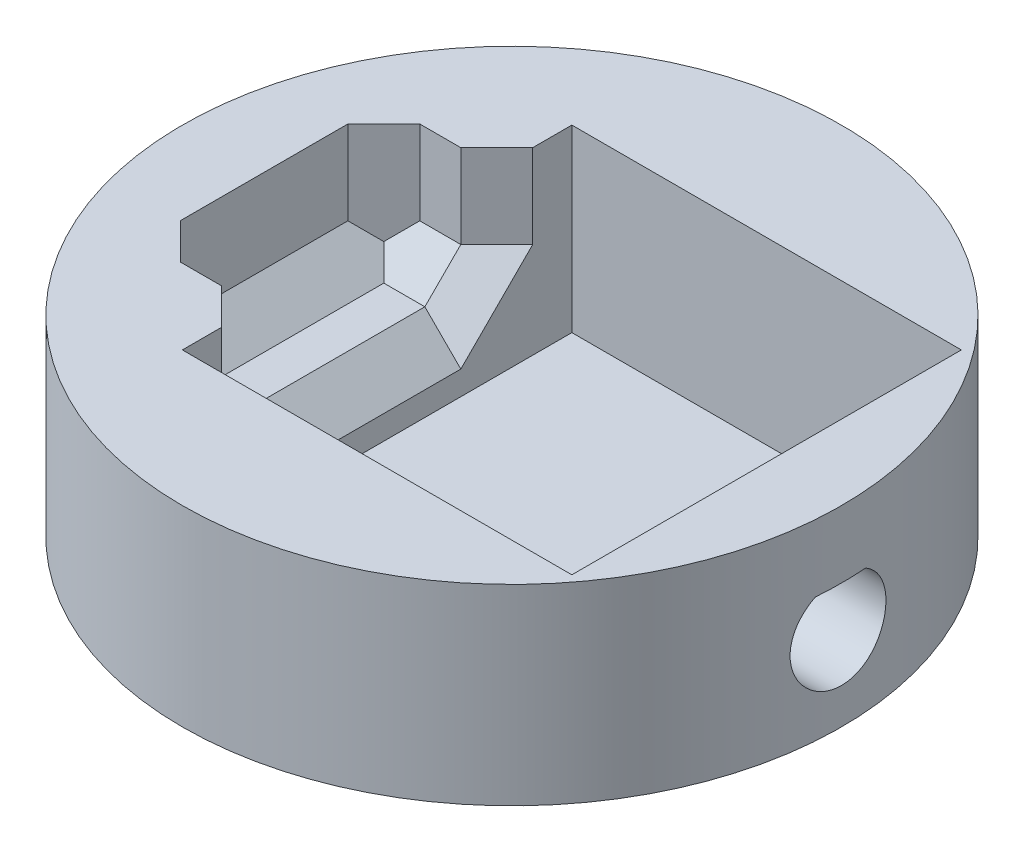
SolidWorks part; units mm, degrees
ref_plane "Front Plane" through (0, 0, 0) normal (0, 0, 1) x (1, 0, 0)
ref_plane "Top Plane" through (0, 0, 0) normal (0, 1, 0) x (1, 0, 0)
ref_plane "Right Plane" through (0, 0, 0) normal (1, 0, 0) x (0, 0, -1)
sketch "Sketch1" plane through (0, 0, 0) normal (0, 1, 0) x (1, 0, 0)
  circle A0 centre (0, 0) radius 27.5
  dimension "D1" = 55
extrude "Boss-Extrude1" add sketch "Sketch1" along normal blind 16
sketch "Sketch3" plane through (0, 16, 0) normal (0, 1, 0) x (1, 0, 0)
  line L0 (21.25, 0) -> (27.5, 0) construction
  line L1 (-11.25, -16.25) -> (16.25, -16.25)
  line L2 (-16.25, -16.25) -> (-16.25, 16.25) construction
  line L3 (-11.25, 16.25) -> (16.25, 16.25) construction
  line L4 (16.25, -16.25) -> (16.25, -1.9281) construction
  line L5 (-11.25, -11.25) -> (0, 0) construction
  line L6 (-11.25, 11.25) -> (0, 0) construction
  line L7 (0, 0) -> (16.25, 0) construction
  line L8 (21.25, 0) -> (27.5, 0) construction
  line L9 (-16.25, 16.25) -> (-11.25, 16.25) construction
  line L10 (16.25, 16.25) -> (21.25, 16.25)
  line L11 (16.25, 0) -> (16.25, -16.25) construction
  line L12 (16.25, -16.25) -> (21.25, -16.25)
  line L13 (21.25, 16.25) -> (21.25, -16.25)
  line L14 (-16.25, 16.25) -> (-11.25, 16.25) construction
  line L15 (-16.25, 16.25) -> (-16.25, -16.25) construction
  line L16 (-16.25, -16.25) -> (-11.25, -16.25) construction
  line L17 (-11.25, 16.25) -> (-11.25, -16.25)
  line L18 (-16.25, 16.25) -> (-11.25, 16.25) construction
  line L19 (-16.25, 16.25) -> (-11.25, 11.25) construction
  line L20 (-16.25, -16.25) -> (-11.25, -11.25) construction
  line L21 (-16.25, -16.25) -> (-11.25, -16.25) construction
  line L22 (0, 0) -> (16.25, 0) construction
  line L23 (16.25, 6.8206) -> (16.25, 16.25) construction
  line L24 (16.25, 16.25) -> (16.25, 0) construction
  line L25 (16.25, 0) -> (21.25, 0) construction
  line L26 (16.25, 0) -> (21.25, 0) construction
  line L27 (0, 0) -> (16.25, 16.25) construction
  line L28 (0, 0) -> (16.25, -16.25) construction
  line L29 (-11.25, 16.25) -> (16.25, 16.25)
  circle A0 centre (0, 0) radius 27.5 construction
  point P1 (0, 0)
  dimension "D1" = 32.5
  dimension "D2" = 32.5
  dimension "D3" = 27.5
  dimension "D5" = 5
  dimension "D6" = 5
extrude "Cut-Extrude1" cut sketch "Sketch3" against normal blind 15
sketch "Sketch4" plane through (21.25, 0, 0) normal (-1, 0, 0) x (0, 0, 1)
  line L0 (0, 3) -> (0, 7) construction
  line L1 (16.25, 1) -> (-16.25, 1) construction
  line L2 (0, 1) -> (0, 3) construction
  line L3 (-2.1032, 10.4024) -> (2.1032, 10.4024)
  arc A0 (-2.1032, 10.4024) -> (2.1032, 10.4024) centre (0, 7) ccw
  arc A1 (2.1032, 10.4024) -> (-2.1032, 10.4024) centre (0, 7) ccw construction
  dimension "D2" = 8
  dimension "D1" = 6
extrude "Cut-Extrude2" cut sketch "Sketch4" against normal blind 15
sketch "Sketch6" plane through (0, 16, 0) normal (0, 1, 0) x (1, 0, 0)
  line L0 (-11.25, 16.25) -> (-11.25, -16.25) construction
  line L1 (-20.6746, 9.9839) -> (-1.8254, 9.9839)
  line L2 (-20.6746, 9.9839) -> (-20.6746, -9.9839)
  line L3 (-20.6746, -9.9839) -> (-1.8254, -9.9839)
  line L4 (-1.8254, 9.9839) -> (-1.8254, -9.9839)
  line L5 (-20.6746, 9.9839) -> (-1.8254, -9.9839) construction
  line L6 (-20.6746, -9.9839) -> (-1.8254, 9.9839) construction
  point P0 (-11.25, 0)
extrude "Cut-Extrude4" cut sketch "Sketch6" against normal blind 10
chamfer "Chamfer2" distance 3 angle 45 6 edges at (-15.9623, 6, 9.9839) (-20.6746, 6, 0) (-15.9623, 6, -9.9839) (-11.25, 11, 9.9839) (-11.25, 11, -9.9839) (-11.25, 6, 0)
chamfer "Chamfer3" distance 3 angle 45 2 edges at (-20.6746, 12.5, -9.9839) (-20.6746, 12.5, 9.9839)
